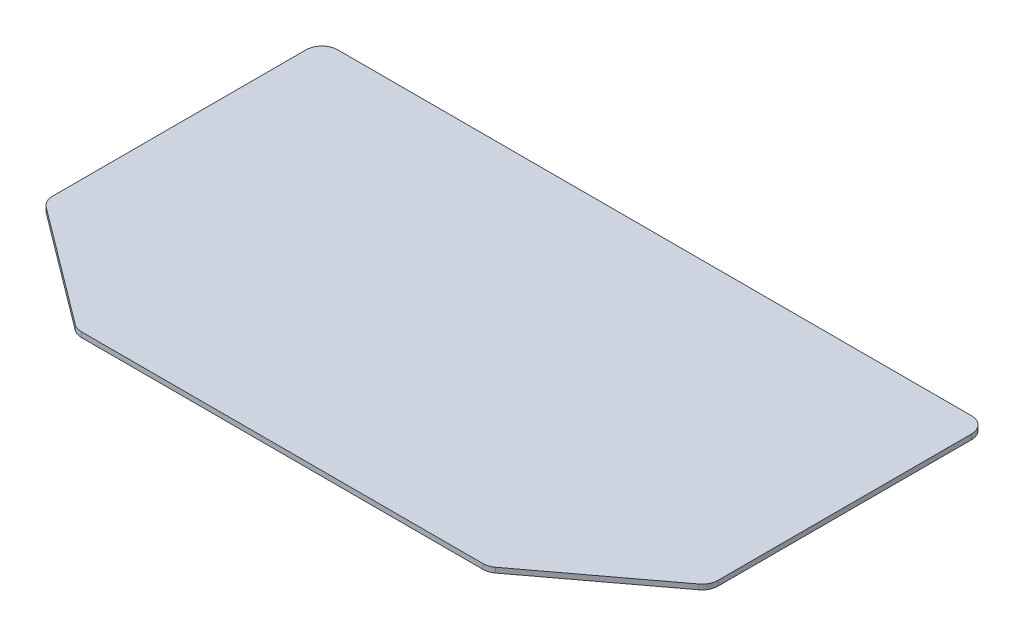
SolidWorks part; units mm, degrees
ref_plane "Front Plane" through (0, 0, 0) normal (0, 0, 1) x (1, 0, 0)
ref_plane "Top Plane" through (0, 0, 0) normal (0, 1, 0) x (1, 0, 0)
ref_plane "Right Plane" through (0, 0, 0) normal (1, 0, 0) x (0, 0, -1)
sketch "Sketch1" plane through (0, 0, 0) normal (0, 1, 0) x (1, 0, 0)
  line L0 (0, 235) -> (0, 60)
  line L1 (0, 0) -> (420, 0) construction
  line L2 (0, 0) -> (0, 235) construction
  line L3 (0, 235) -> (420, 235) construction
  line L4 (420, 0) -> (420, 235) construction
  line L5 (0, 60) -> (80, 0)
  line L6 (80, 0) -> (340, 0)
  line L7 (340, 0) -> (420, 60)
  line L8 (420, 60) -> (420, 235)
  line L9 (420, 235) -> (0, 235)
  line L10 (210, 0) -> (210, 235) construction
  point P11 (72.7501, 0)
  dimension "D1" = 420
  dimension "D2" = 235
  dimension "D3" = 60
  dimension "D4" = 80
extrude "Boss-Extrude1" add sketch "Sketch1" along normal blind 3.175
fillet "Fillet1" radius 10 6 edges at (80, 1.5875, 0) (0, 1.5875, -60) (0, 1.5875, -235) (420, 1.5875, -235) (420, 1.5875, -60) (340, 1.5875, 0)
sketch "Sketch2" plane through (0, 3.175, 0) normal (0, 1, 0) x (1, 0, 0)
  line L0 (0, 225) -> (0, 65) construction
  line L1 (0, 220.0764) -> (3.175, 220.0764) construction
  line L2 (0, 220.0764) -> (0, 73.6084) construction
  line L3 (0, 73.6084) -> (3.175, 73.6084) construction
  line L4 (3.175, 220.0764) -> (3.175, 73.6084) construction
  line L5 (12.8705, 50.3471) -> (14.7755, 52.8871) construction
  line L6 (4, 57) -> (77.3333, 2) construction
  line L7 (14.7755, 52.8871) -> (73.1239, 9.1258) construction
  line L8 (73.1239, 9.1258) -> (71.2189, 6.5858) construction
  line L9 (71.2189, 6.5858) -> (12.8705, 50.3471) construction
  line L10 (410, 235) -> (10, 235) construction
  line L11 (30.9486, 235) -> (389.7599, 235) construction
  line L12 (30.9486, 235) -> (30.9486, 231.825) construction
  line L13 (30.9486, 231.825) -> (389.7599, 231.825) construction
  line L14 (389.7599, 235) -> (389.7599, 231.825) construction
  line L15 (83.3333, 0) -> (336.6667, 0) construction
  line L16 (95.4463, 0) -> (320.7836, 0) construction
  line L17 (95.4463, 0) -> (95.4463, 3.175) construction
  line L18 (95.4463, 3.175) -> (320.7836, 3.175) construction
  line L19 (320.7836, 0) -> (320.7836, 3.175) construction
  dimension "D1" = 3.175
